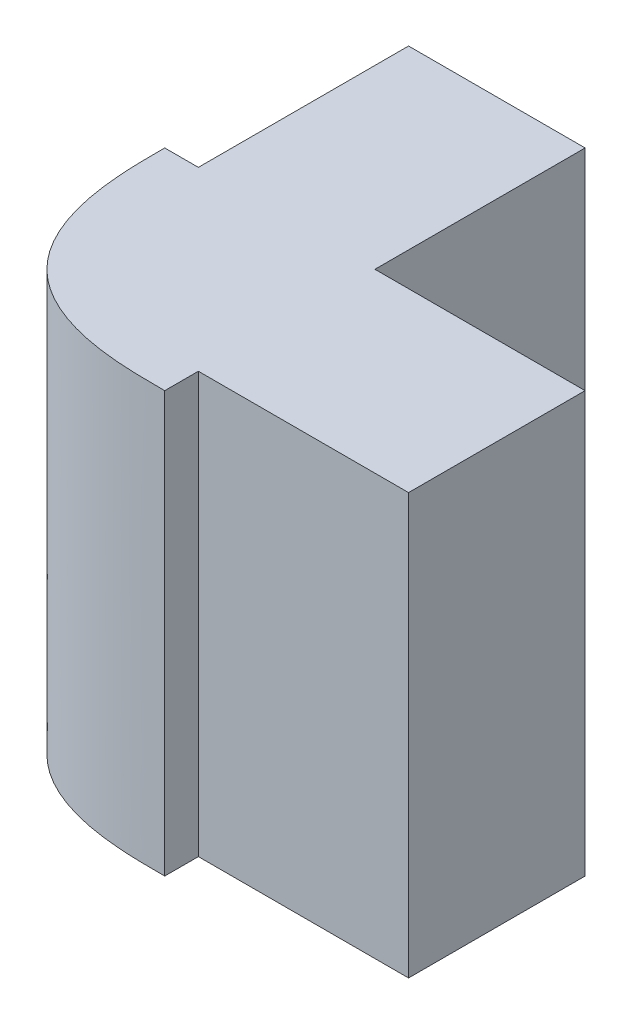
SolidWorks part; units mm, degrees
ref_plane "Front Plane" through (0, 0, 0) normal (0, 0, 1) x (1, 0, 0)
ref_plane "Top Plane" through (0, 0, 0) normal (0, 1, 0) x (1, 0, 0)
ref_plane "Right Plane" through (0, 0, 0) normal (1, 0, 0) x (0, 0, -1)
sketch "Sketch2" plane through (0, 0, 0) normal (0, 1, 0) x (1, 0, 0)
  line L0 (-20, -40) -> (-20, -36.8)
  line L1 (-20, 20) -> (20, 20) construction
  line L2 (-20, 20) -> (-20, -20) construction
  line L3 (-20, -20) -> (20, -20) construction
  line L4 (20, 20) -> (20, -20) construction
  line L5 (-20, 20) -> (20, -20) construction
  line L6 (-20, -20) -> (20, 20) construction
  line L7 (-20, -36.8) -> (0, -36.8)
  line L8 (-40, -20) -> (-36.8, -20)
  line L9 (-36.8, -20) -> (-36.8, 0)
  line L10 (-20, -40) -> (-40, -40)
  line L11 (-40, -20) -> (-40, -40)
  line L12 (-36.8, 0) -> (-20, 0)
  line L13 (-20, 0) -> (-20, -20)
  line L14 (-20, -20) -> (0, -20)
  line L15 (0, -20) -> (0, -36.8)
  point P0 (0, 0)
  point P15 (-10, -36.8)
  point P17 (0, -20)
  dimension "D1" = 40
  dimension "D2" = 3.2
  dimension "D3" = 10
  dimension "D4" = 20
extrude "Boss-Extrude1" add sketch "Sketch2" along normal blind 40
fillet "Fillet1" radius 20 1 edges at (-40, 20, 40) curvature continuous yes
equation "\"structural_panel_corner_radius\"= 20mm"
equation "\"cosmetic_panel_corner_radius\"= 30mm"
equation "\"cosmetic_panel_thickness\"= 3.2mm"
equation "\"total_distance_from_frame\"= 20mm'used to provide additional space for insulation. total distance from the aluminum extrusion frame to the outer surface of the cosmetic panels."
equation "\"extra_length_x\"= 0mm'additional offsets in x,y,z to move the edges past the extrusion frame (e.g. for door or feet)"
equation "\"extra_length_y\"= 0mm"
equation "\"extra_length_z\"= 0mm"
equation "\"cosmetric_panel_hole_offset\"= 10mm'how far the cosmetic panel mounting holes are from the edge. sets the lip size"
equation "\"D2@Sketch2\"=\"cosmetic_panel_thickness\""
equation "\"D3@Sketch2\"=\"cosmetric_panel_hole_offset\""
equation "\"D4@Sketch2\"=\"total_distance_from_frame\""
equation "\"edge_radius\"= ( 20mm - ( 2 * \"cosmetric_panel_hole_offset\" ) ) + \"total_distance_from_frame\"'the final edge radius, derived from other variables"
equation "\"D1@Fillet1\"=\"edge_radius\""
